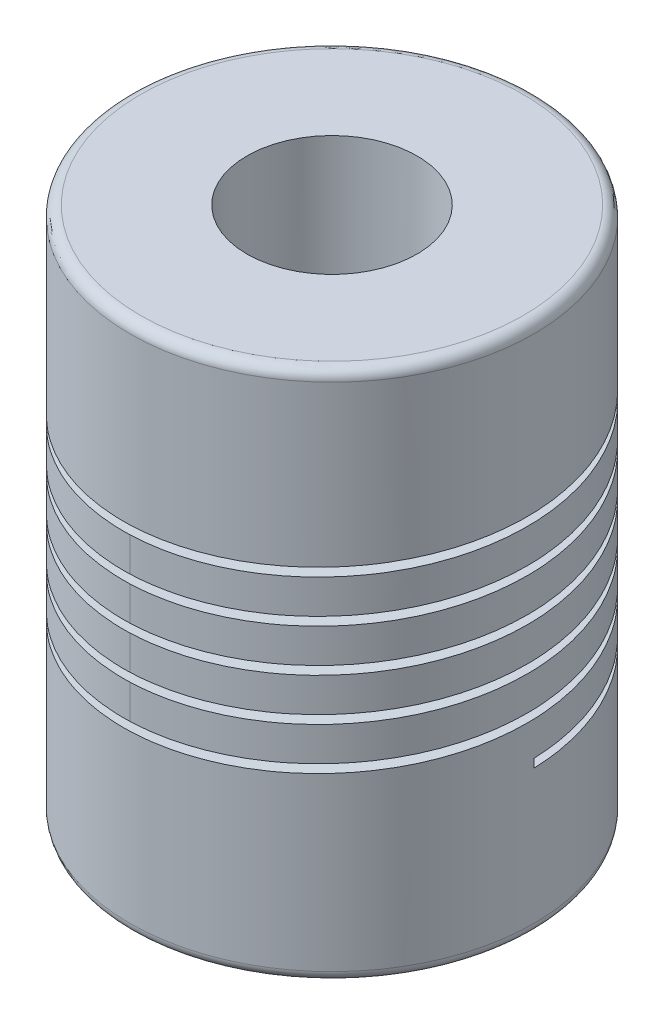
SolidWorks part; units mm, degrees
ref_plane "Front" through (0, 0, 0) normal (0, 0, 1) x (1, 0, 0)
ref_plane "Top" through (0, 0, 0) normal (0, 1, 0) x (1, 0, 0)
ref_plane "Right" through (0, 0, 0) normal (1, 0, 0) x (0, 0, -1)
sketch "Sketch1" plane through (0, 0, 0) normal (0, 1, 0) x (1, 0, 0)
  circle A0 centre (0, 0) radius 9.5
  circle A1 centre (0, 0) radius 2.5
extrude "Boss-Extrude1" add sketch "Sketch1" along normal blind 25
sketch "Sketch2" plane through (0, 25, 0) normal (0, 1, 0) x (1, 0, 0)
  circle A0 centre (0, 0) radius 4
extrude "Cut-Extrude1" cut sketch "Sketch2" against normal blind 18
fillet "Fillet1" radius 0.5 2 edges at (0, 0, 9.5) (0, 25, 9.5)
ref_plane "Plane1" through (0, 18, 0) normal (0, 1, 0) x (1, 0, 0)
sketch "Sketch3" plane through (0, 18, 0) normal (0, 1, 0) x (1, 0, 0)
  circle A0 centre (0, 0) radius 9.5
curve "Helix/Spiral1" pitch 2 height 11 turns 5.5
sketch "Sketch4" plane through (0, 0, 0) normal (0, 0, 1) x (1, 0, 0)
  line L0 (-9.5, 18.2222) -> (-2.5, 18)
  line L1 (-9.5, 24.5) -> (-9.5, 0.5) construction
  line L2 (9.9, 18) -> (-9.9, 18) construction
  line L3 (-2.5, 18) -> (-9.5, 17.8222)
  line L4 (-9.5, 17.8222) -> (-9.5, 18.2222)
  dimension "D1" = 0.4
  dimension "D2" = 7
sweep "Cut-Sweep2" cut profiles "Sketch4" path "Helix/Spiral1"
